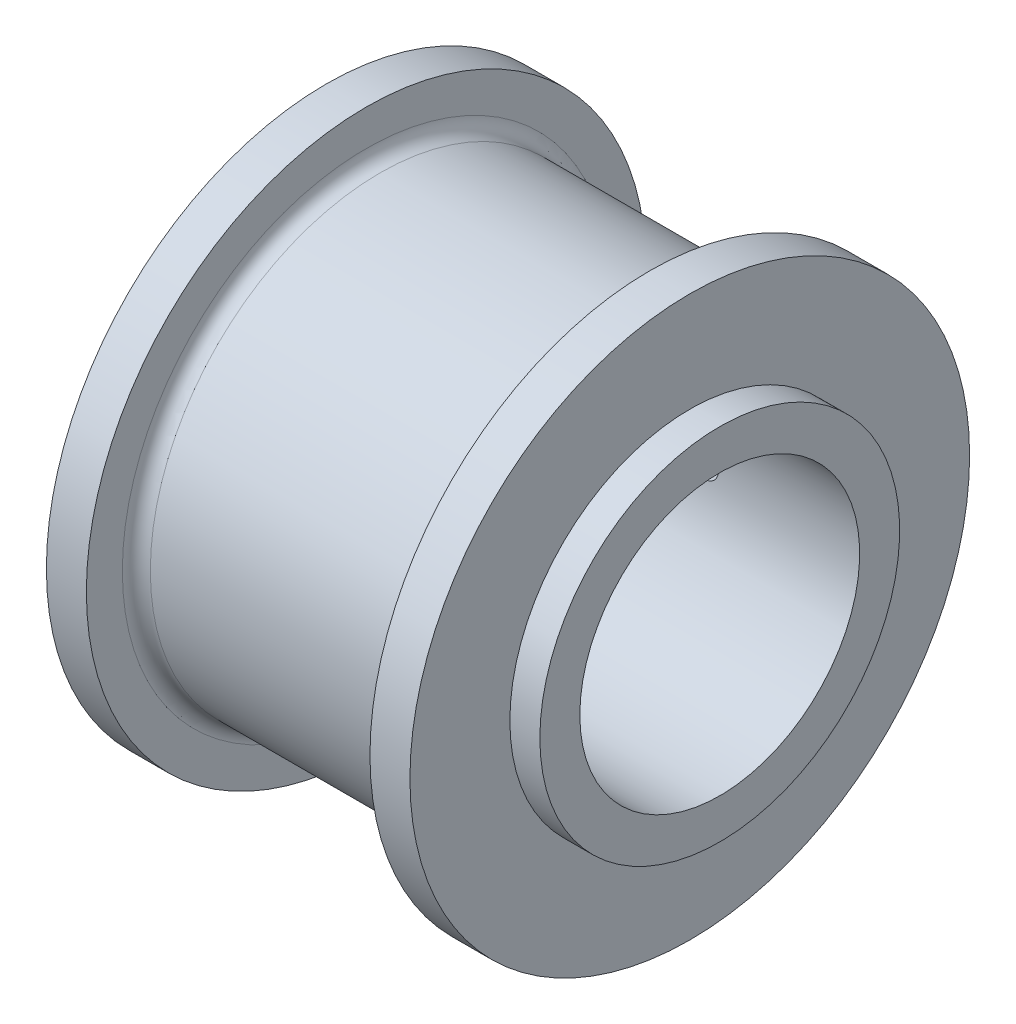
SolidWorks part; units mm, degrees
ref_plane "Front Plane" through (0, 0, 0) normal (0, 0, 1) x (1, 0, 0)
ref_plane "Top Plane" through (0, 0, 0) normal (0, 1, 0) x (1, 0, 0)
ref_plane "Right Plane" through (0, 0, 0) normal (1, 0, 0) x (0, 0, -1)
sketch "Sketch1" plane through (0, 0, 0) normal (0, 0, 1) x (1, 0, 0)
  line L0 (3.81, 35.56) -> (8.89, 35.56)
  line L1 (8.89, 35.56) -> (8.89, 30.988)
  line L3 (44.925, 30.988) -> (44.925, 35.56)
  line L4 (44.925, 35.56) -> (50.005, 35.56)
  line L5 (50.005, 35.56) -> (50.005, 22.86)
  line L6 (50.005, 22.86) -> (53.815, 22.86)
  line L7 (53.815, 22.86) -> (53.815, 17.78)
  line L8 (53.815, 17.78) -> (15.08, 17.78)
  line L9 (15.08, 17.78) -> (15.08, 16.002)
  line L10 (15.08, 16.002) -> (5.08, 16.002)
  line L11 (5.08, 16.002) -> (5.08, 11.08)
  line L12 (5.08, 11.08) -> (0, 11.08)
  line L13 (0, 11.08) -> (0, 22.86)
  line L14 (0, 22.86) -> (3.81, 22.86)
  line L15 (3.81, 22.86) -> (3.81, 35.56)
  line L16 (0, 0) -> (18.9296, 0) construction
  line L18 (10.668, 29.21) -> (43.147, 29.21)
  arc A0 (44.925, 30.988) -> (43.147, 29.21) centre (43.147, 30.988) cw
  arc A1 (8.89, 30.988) -> (10.668, 29.21) centre (10.668, 30.988) ccw
  point P2 (44.925, 29.21)
  point P19 (9.4648, 0)
  point P20 (41.7928, 30.32)
  point P21 (13.97, 29.21)
  point P23 (14.599, 29.21)
  point P24 (44.5359, 29.21)
  dimension "D4" = 1.778
  dimension "D2" = 10
  dimension "D3" = 38.735
  dimension "D1" = 16.002
  dimension "D5" = 17.78
  dimension "D6" = 22.86
  dimension "D7" = 22.86
  dimension "D8" = 5.08
  dimension "D9" = 35.56
  dimension "D10" = 35.56
  dimension "D14" = 3.81
  dimension "D15" = 3.81
  dimension "D16" = 5.08
  dimension "D11" = 29.21
  dimension "D12" = 11.08
revolve "Revolve1" add sketch "Sketch1" angle 360 about L16
ref_plane "Plane1" through (34.257, 0, 0) normal (1, 0, 0) x (0, 0, -1)
sketch "Sketch2" plane through (34.257, 0, 0) normal (1, 0, 0) x (0, 0, -1)
  point P0 (0, 0)
ref_plane "Plane2" through (0, 0, -29.21) normal (0, 0, -1) x (-1, 0, 0)
sketch "Sketch3" plane through (0, 0, -29.21) normal (0, 0, -1) x (-1, 0, 0)
  line L0 (0, 0) -> (-31.082, 0) construction
  line L1 (-37.432, 25.4) -> (-31.082, 25.4)
  line L2 (-37.432, 25.4) -> (-37.432, -25.4)
  line L3 (-37.432, -25.4) -> (-31.082, -25.4)
  line L4 (-31.082, 25.4) -> (-31.082, -25.4)
  line L5 (-34.257, 0) -> (-34.257, 25.4) construction
  point P4 (0, 0)
  point P8 (-34.257, 0)
  dimension "D1" = 50.8
  dimension "D2" = 6.35
extrude "Cut-Extrude1" cut sketch "Sketch3" against normal blind 2.54
sketch "Sketch4" plane through (0, 0, -29.21) normal (0, 0, -1) x (-1, 0, 0)
  point P0 (-34.257, 0)
hole_wizard "1/8 (0.125) Diameter Hole1" positions "Sketch4" profile "Sketch5" hole size "1/8" standard "ANSI Inch" end condition up to next
sketch "Sketch5" plane through (34.257, 0, -29.21) normal (1, 0, 0) x (0, 1, 0)
  line L0 (0, 0) -> (0, 11.43)
  line L1 (0, 11.43) -> (1.5875, 11.43)
  line L2 (1.5875, 11.43) -> (1.5875, 0)
  line L5 (1.5875, 0) -> (0, 0)
  line L11 (0, -6.35) -> (0, 107.95) construction
  dimension "Thru Hole Dia." = 3.175
  dimension "Thru Hole Depth" = 11.43
equation "\"bearing_radius\"= 0.629921"
equation "\"bearing_width\"=0.393701"
equation "\"D2@Sketch1\"=\"bearing_width\""
equation "\"kero_radius\"=0.334in"
equation "\"lox_radius\"=0.23622in"
equation "\"Cavity_width\"=0.031in"
equation "\"tooth_width\"=0.01in"
equation "\"cavity_depth\"=0.031in"
equation "\"seal_step\"=0.01in"
equation "\"purge_length\"=0.04in"
equation "\"insert_radius\" = 0.7in"
equation "\"recycle_groove width\" = 0.06in"
equation "\"recycle_groove_depth\" = 0.06in"
equation "\"N2_purge_width\"= .06in"
equation "\"N2_purge_depth\"= .06in"
equation "\"drain_width\"= .06in"
equation "\"drain_depth\"= .06in"
equation "\"radial_clearance\"= .002in"
equation "\"IPS_flange_width\"= .2in"
equation "\"IPS_flange_radius\" = 1.4in"
equation "\"IPS_LOX_male_radius\"= .9in"
equation "\"IPS_Kero_male_radius\" = .9in"
equation "\"IPS_radius\"= 1.15in"
equation "\"D5@Sketch1\"=\"insert_radius\""
equation "\"InsertLength\"= 1.525in"
equation "\"D3@Sketch1\"=\"InsertLength\""
equation "\"D6@Sketch1\"=\"IPS_Kero_male_radius\""
equation "\"D7@Sketch1\"=\"IPS_LOX_male_radius\""
equation "\"D8@Sketch1\"=\"IPS_flange_width\""
equation "\"D9@Sketch1\"=\"IPS_flange_radius\""
equation "\"D10@Sketch1\"=\"IPS_flange_radius\""
equation "\"D12@Sketch1\"=\"lox_radius\"+.2"
